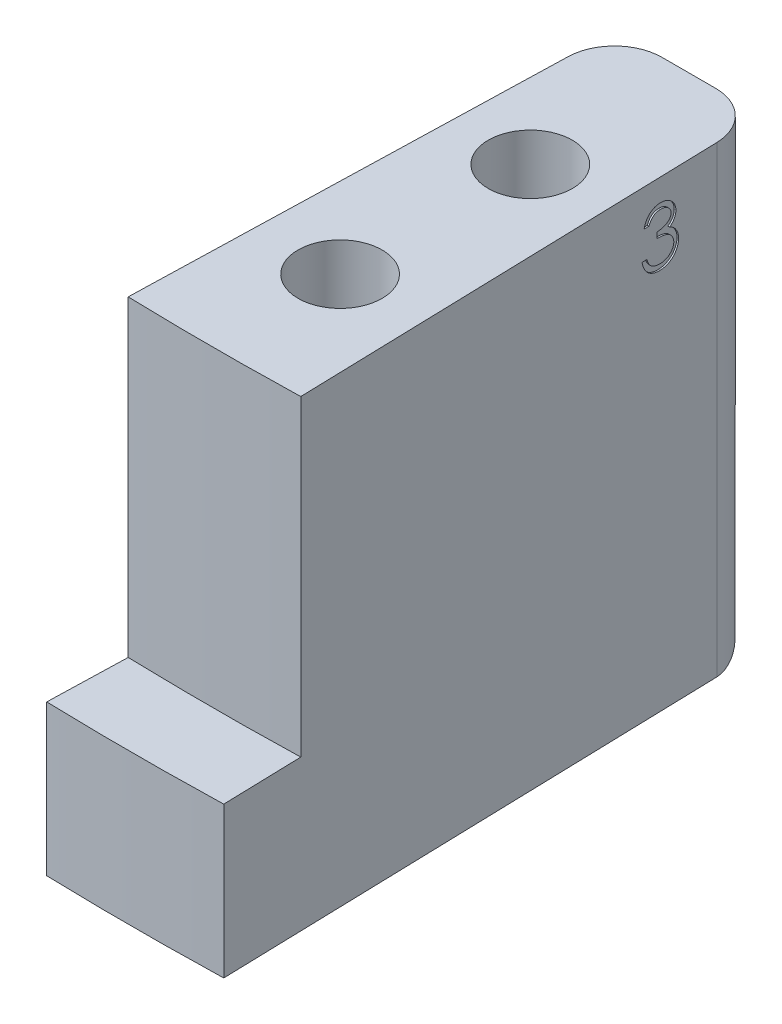
SolidWorks part; units mm, degrees
ref_plane "前视基准面" through (0, 0, 0) normal (0, 0, 1) x (1, 0, 0)
ref_plane "上视基准面" through (0, 0, 0) normal (0, 1, 0) x (1, 0, 0)
ref_plane "右视基准面" through (0, 0, 0) normal (1, 0, 0) x (0, 0, -1)
ref_axis "顶盖中心轴" through (0, -55, 0) along (0, 1, 0)
sketch "草图1" plane through (0, 0, 0) normal (0, 1, 0) x (1, 0, 0)
  line L0 (-4.7487, -170.0072) -> (-4.8586, -173.9402) construction
  line L1 (0, 0) -> (0, -125.794) construction
  line L3 (-4.6089, -165) -> (4.6089, -165)
  line L4 (-4.6089, -165) -> (-5.5843, -199.922)
  line L5 (4.6089, -165) -> (5.5843, -199.922)
  arc A0 (-5.4447, -194.924) -> (5.4447, -194.924) centre (0, 0) ccw
  arc A1 (-5.5843, -199.922) -> (5.5843, -199.922) centre (0, 0) ccw
  dimension "D1" = 1.6
  dimension "D2" = 195
  dimension "D4" = 200
  dimension "D3" = 165
extrude "主体" add sketch "草图1" along normal blind 29.2 contours L4 A0 L5 L3 region at (0, 0, 180.4033)
extrude "插销" add sketch "草图1<3>" along normal blind 9.5 contours L4 A1 L5 A0 region at (0, 0, 197.4849)
sketch "草图1<3>" plane through (0, 0, 0) normal (0, 1, 0) x (1, 0, 0) same geometry as "草图1"
ref_plane "对称面" through (0, 0, 0) normal (1, 0, 0) x (0, 0, -1)
fillet "圆角1" radius 3 3 edges at (-4.6089, 14.6, 165) (4.6089, 14.6, 165) (0, 0, 165)
hole_wizard "M5 间隙孔1" positions "草图4" profile "草图5" hole size "M5" standard "ISO" end condition up to next
sketch "草图4" plane through (0, 29.2, 0) normal (0, 1, 0) x (1, 0, 0)
  line L0 (0, -13.75) -> (0, 13.75) construction
  point P0 (0, -187)
  point P2 (0, -175)
  dimension "D1" = 175
  dimension "D2" = 187
sketch "草图5" plane through (0, 29.2, 187) normal (1, 0, 0) x (0, 0, 1)
  line L0 (0, 0) -> (0, 29.2)
  line L1 (0, 29.2) -> (2.65, 29.2)
  line L2 (2.65, 29.2) -> (2.65, 0)
  line L5 (2.65, 0) -> (0, 0)
  line L11 (0, -6.35) -> (0, 107.95) construction
  dimension "通孔孔直径" = 5.3
  dimension "通孔孔深度" = 29.2
sketch "草图6" plane through (0, 0, 0) normal (0, -1, 0) x (1, 0, 0)
  line L1 (0, 179.792) -> (-4.15, 177.396)
  line L2 (-4.15, 177.396) -> (-4.15, 172.604)
  line L3 (-4.15, 172.604) -> (0, 170.208)
  line L4 (0, 170.208) -> (4.15, 172.604)
  line L5 (4.15, 172.604) -> (4.15, 177.396)
  line L6 (4.15, 177.396) -> (0, 179.792)
  line L7 (0, 191.792) -> (-4.15, 189.396)
  line L8 (-4.15, 189.396) -> (-4.15, 184.604)
  line L9 (-4.15, 184.604) -> (0, 182.208)
  line L10 (0, 182.208) -> (4.15, 184.604)
  line L11 (4.15, 184.604) -> (4.15, 189.396)
  line L12 (4.15, 189.396) -> (0, 191.792)
  circle A0 centre (0, 175) radius 4.15 construction
  circle A1 centre (0, 187) radius 4.15 construction
  point P9 (0, 182.208)
  point P17 (0, 170.208)
  dimension "D1" = 8.3
  dimension "D2" = 8.3
extrude "切除-拉伸1" cut sketch "草图6" against normal blind 5
sketch "草图7" plane through (0, 0, 0) normal (0.9996, 0, -0.0279) x (-0.0279, 0, -0.9996)
  line L0 (-167.9817, 0.0012) -> (-167.9817, 29.2) construction
  line L2 (-167.9817, 29.2) -> (-195, 29.2) construction
  text T0 "3\r\n"
  point P1 (0, 0)
  point P4 (0, 0)
  point P6 (-170.6934, 29.6)
  dimension "D1" = 5
  dimension "D2" = 5
extrude "切除-拉伸2" cut sketch "草图7" against normal blind 0.1
